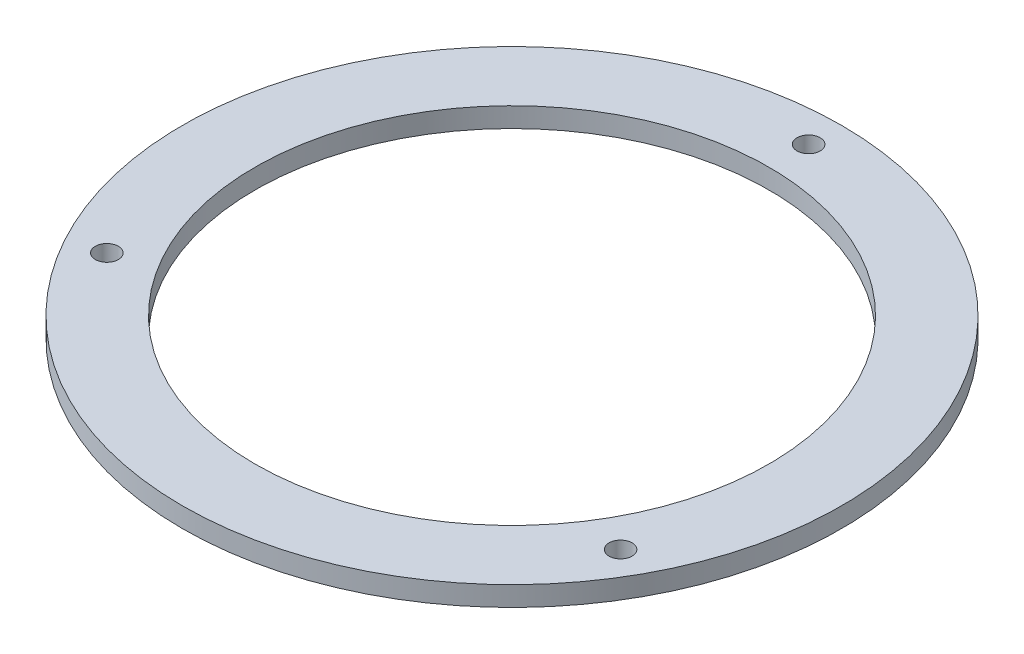
SolidWorks part; units mm, degrees
ref_plane "Front Plane" through (0, 0, 0) normal (0, 0, 1) x (1, 0, 0)
ref_plane "Top Plane" through (0, 0, 0) normal (0, 1, 0) x (1, 0, 0)
ref_plane "Right Plane" through (0, 0, 0) normal (1, 0, 0) x (0, 0, -1)
sketch "Sketch1" plane through (0, 0, 0) normal (0, 1, 0) x (1, 0, 0)
  circle A0 centre (0, 0) radius 39
  circle A1 centre (0, 0) radius 50
  circle A2 centre (0, 0) radius 45 construction
  circle A3 centre (0, 45) radius 1.75
  circle A4 centre (38.9711, -22.5) radius 1.75
  circle A5 centre (-38.9711, -22.5) radius 1.75
  point P13 (0, 0)
  dimension "D1" = 100
  dimension "D2" = 78
  dimension "D3" = 90
  dimension "D4" = 3.5
  dimension "D5" = 3
extrude "Boss-Extrude1" add sketch "Sketch1" along normal blind 3
